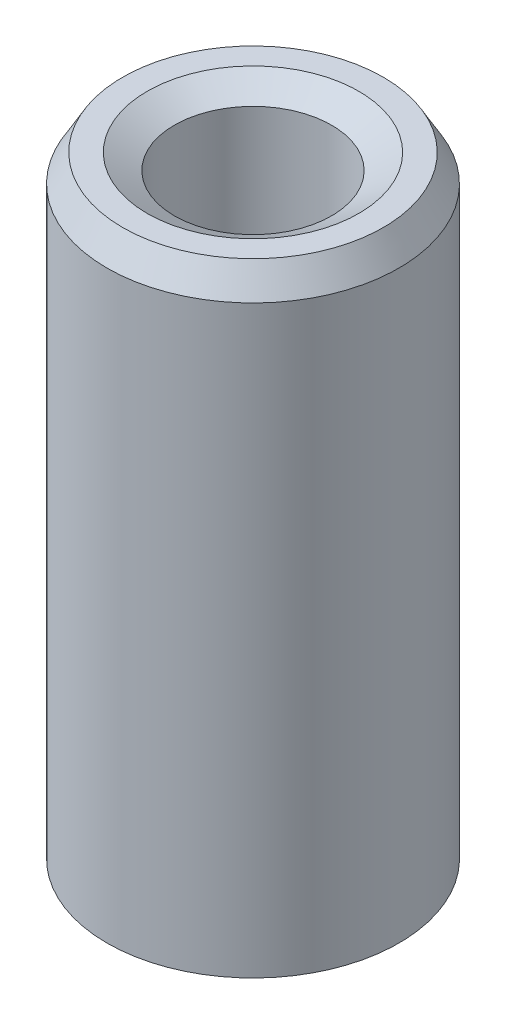
SolidWorks part; units mm, degrees
ref_plane "Front Plane" through (0, 0, 0) normal (0, 0, 1) x (1, 0, 0)
ref_plane "Top Plane" through (0, 0, 0) normal (0, 1, 0) x (1, 0, 0)
ref_plane "Right Plane" through (0, 0, 0) normal (1, 0, 0) x (0, 0, -1)
sketch "Sketch1" plane through (0, 0, 0) normal (0, 1, 0) x (1, 0, 0)
  circle A0 centre (0, 0) radius 5
  dimension "SLEEVE_OD" = 10
extrude "Boss-Extrude1" add sketch "Sketch1" along normal blind 21.4899
sketch "Sketch2" plane through (0, 0, 0) normal (0, 1, 0) x (1, 0, 0)
  circle A0 centre (0, 0) radius 2.6923
  dimension "BORE_D" = 5.3845
extrude "Cut-Extrude1" cut sketch "Sketch2" along normal through all
chamfer "Chamfer1" distance 0.9322 angle 30 4 edges at (0, 21.4899, 2.6923) (0, 0, 2.6923) (0, 0, 5) (0, 21.4899, 5) first distance on face at (0, 21.4899, 2.6923) first distance on face at (0, 0, 2.6923) first distance on face at (0, 21.4899, 5)
